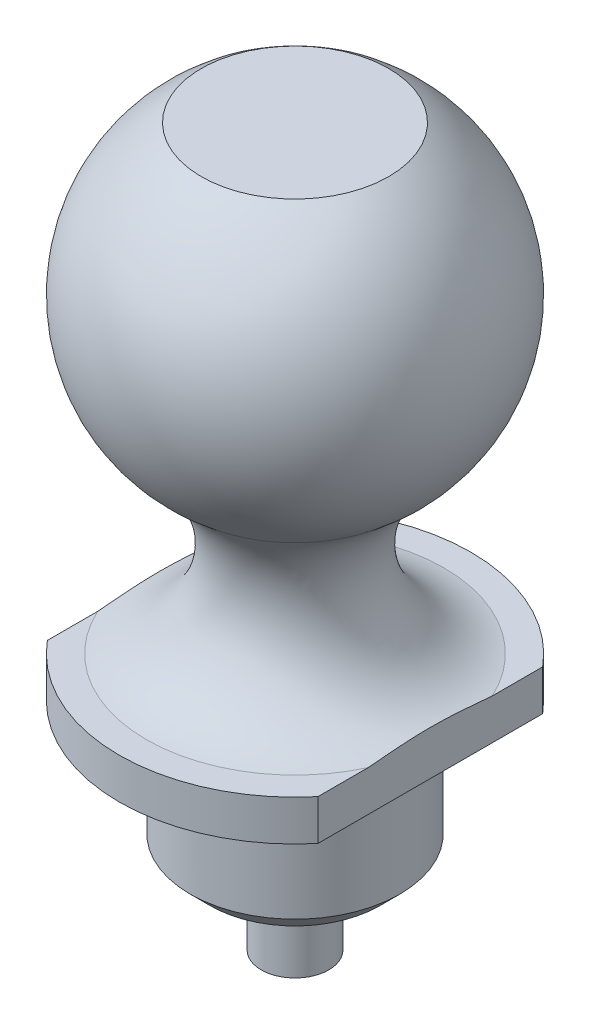
SolidWorks part; units mm, degrees
ref_plane "Front Plane" through (0, 0, 0) normal (0, 0, 1) x (1, 0, 0)
ref_plane "Top Plane" through (0, 0, 0) normal (0, 1, 0) x (1, 0, 0)
ref_plane "Right Plane" through (0, 0, 0) normal (1, 0, 0) x (0, 0, -1)
sketch "Sketch1" plane through (0, 0, 0) normal (0, 0, 1) x (1, 0, 0)
  line L0 (30, 5.9) -> (30, -5.9) construction
  line L1 (30, 5.9) -> (29.4, 6.5) construction
  line L2 (29.4, 6.5) -> (8.3325, 6.5) construction
  line L3 (29.4, -6.5) -> (30, -5.9) construction
  line L4 (10.25, -6.5) -> (29.4, -6.5) construction
  line L5 (9.65, -5.9) -> (10.25, -6.5) construction
  line L6 (8.3325, -5.9) -> (9.65, -5.9) construction
  line L7 (-6.9575, -6.6626) -> (7.1497, -6.6626) construction
  line L8 (-6.4835, -5.7399) -> (-5.5, -9.8399) construction
  line L9 (5.5, -9.8399) -> (6.4835, -5.7399) construction
  line L10 (6.5, -13) -> (6.5, -11.5) construction
  line L11 (6.5, -13) -> (3.4641, -13) construction
  line L12 (4.3047, -13) -> (-4.005, -13) construction
  line L13 (-6.5, -10.6) -> (-6.5, -13) construction
  line L14 (-6.5, -13) -> (-3.4641, -13) construction
  line L17 (-4, -16.4605) -> (-4, -27.0605) construction
  line L18 (-4.005, -13) -> (-4.005, -18.3) construction
  line L19 (-4, -27.0605) -> (-3.1376, -18) construction
  line L20 (-3.1376, -18) -> (3.1376, -18) construction
  line L21 (3.1376, -18) -> (4.3047, -16.8329) construction
  line L22 (4.3047, -13) -> (4.3047, -16.8329)
  line L23 (6.5, -13) -> (6.5, -11.5)
  line L24 (0, -13) -> (0, 0)
  line L25 (0, 0) -> (0, 5.5)
  line L26 (4.3047, -13) -> (6.5, -13)
  line L27 (4.3047, -16.8329) -> (3.1376, -18)
  line L28 (3.1376, -18) -> (0, -18)
  line L29 (0, -18) -> (0, -13)
  line L30 (0, 5.5) -> (3.4641, 5.5)
  line L31 (5.5, -11.5) -> (6.5, -11.5)
  arc A0 (3.9919, -5.1298) -> (3.4641, 5.5) centre (0, 0) ccw
  arc A1 (7.5195, 6.0983) -> (-6.9575, -6.6626) centre (0.1963, -0.1861) ccw construction
  arc A2 (4.9165, -10.3) -> (5.5, -9.8399) centre (4.9165, -9.7) ccw construction
  arc A3 (-5.5, -9.8399) -> (-4.9165, -10.3) centre (-4.9165, -9.7) ccw construction
  arc A4 (-6.5, -10.6) -> (-3.4641, -7.8181) centre (-6.5, -7.5525) ccw construction
  circle A5 centre (6.4074, -10.4219) radius 1.082 construction
  arc A6 (3.9919, -5.1298) -> (5.5, -11.5) centre (6.2022, -7.9701) ccw
  point P33 (6.5, -16.8711)
  point P37 (4.005, -19.1875)
  point P46 (0, 0)
  point P49 (6.8614, -16.2223)
  point P51 (3.7559, -19.8395)
  point P52 (0, 0)
  point P53 (3.8268, -19.8395)
  point P54 (0, 0)
  point P55 (3.1376, -18)
  dimension "D1" = 13
  dimension "D2" = 1.5
  dimension "D3" = 5
  dimension "D4" = 45
revolve "Revolve1" add sketch "Sketch1" angle 360 about L24
ref_axis "Axis1" through (0, 28.3589, 0) along (0, -1, 0)
ref_plane "Plane1" through (0, -18.3, 0) normal (0, -1, 0) x (-1, 0, 0)
sketch "Sketch2" plane through (0, -18.3, 0) normal (0, -1, 0) x (-1, 0, 0)
  line L1 (7.5056, 0) -> (3.7528, 6.5)
  line L2 (3.7528, 6.5) -> (-3.7528, 6.5)
  line L3 (-3.7528, 6.5) -> (-7.5056, 0)
  line L4 (-7.5056, 0) -> (-3.7528, -6.5)
  line L5 (-3.7528, -6.5) -> (3.7528, -6.5)
  line L6 (3.7528, -6.5) -> (7.5056, 0)
  circle A0 centre (0, 0) radius 6.5 construction
  dimension "D1" = 13
extrude "Boss-Extrude1" [suppressed] add sketch "Sketch2" along normal blind 6
sketch "Sketch3" [suppressed] plane through (0, -18.3, 0) normal (0, 1, 0) x (1, 0, 0)
  circle A0 centre (0, 0) radius 6.5
extrude "Cut-Extrude2" [suppressed] cut sketch "Sketch3" against normal blind 6 draft 50 flip side to cut
sketch "Sketch4" [suppressed] plane through (0, -24.3, 0) normal (0, -1, 0) x (1, 0, 0)
  circle A0 centre (0, 0) radius 6.5
  dimension "D1" = 13
extrude "Cut-Extrude3" [suppressed] cut sketch "Sketch4" against normal blind 6 draft 50 flip side to cut
fillet "Fillet1" [suppressed] radius 0.5
sketch "Sketch5" plane through (0, -13, 0) normal (0, -1, 0) x (1, 0, 0)
  line L0 (-5, 4.1533) -> (-5, -4.1533)
  line L2 (5, -4.1533) -> (5, 4.1533)
  circle A0 centre (0, 0) radius 6.5 construction
  arc A1 (5, -4.1533) -> (5, 4.1533) centre (0, 0) ccw
  arc A2 (-5, 4.1533) -> (-5, -4.1533) centre (0, 0) ccw
  dimension "D1" = 10
  dimension "D2" = 5
extrude "Cut-Extrude4" cut sketch "Sketch5" against normal blind 5
sketch "Croquis1" plane through (0, -18, 0) normal (0, -1, 0) x (-1, 0, 0)
  circle A0 centre (0, 0) radius 1.25
  dimension "D1" = 2.5
extrude "Saliente-Extruir1" add sketch "Croquis1" along normal blind 3
sketch "Croquis2" plane through (0, -18, 0) normal (0, -1, 0) x (1, 0, 0)
  line L0 (5, 4.1533) -> (5, -4.1533) construction
  circle A0 centre (0, 0) radius 3.875
  circle A1 centre (0, 0) radius 5
  dimension "D1" = 7.75
extrude "Cortar-Extruir2" cut sketch "Croquis2" against normal up to surface (5 mm away) up to face at (0, -13, 0)
